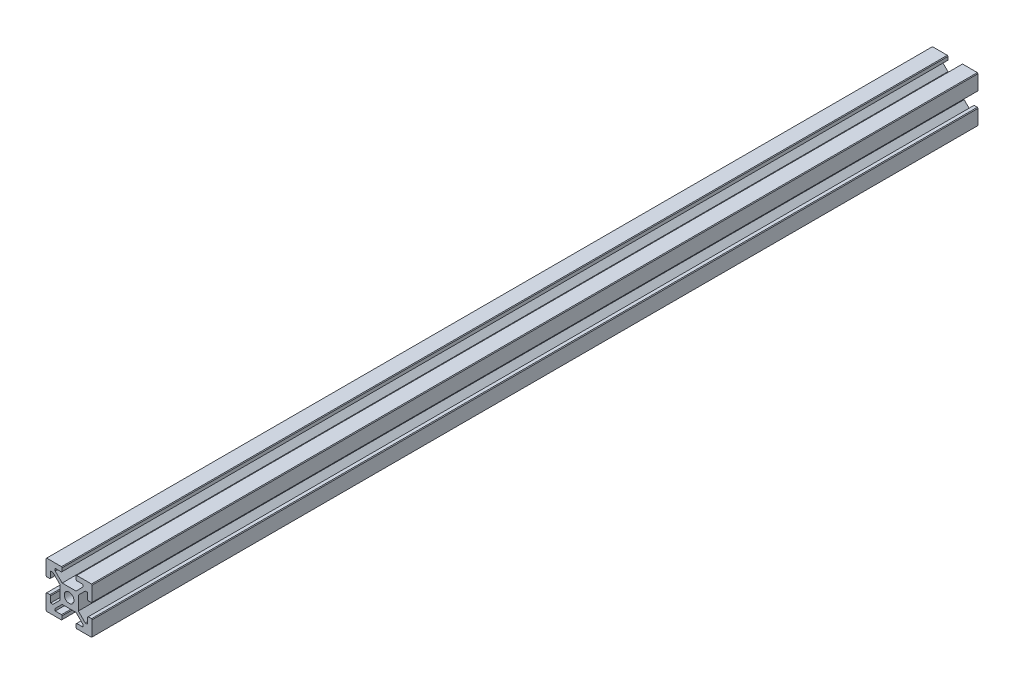
SolidWorks part; units mm, degrees
ref_plane "Front" through (0, 0, 0) normal (0, 0, 1) x (1, 0, 0)
ref_plane "Top" through (0, 0, 0) normal (0, 1, 0) x (1, 0, 0)
ref_plane "Right" through (0, 0, 0) normal (1, 0, 0) x (0, 0, -1)
sketch "Sketch1" plane through (0, 0, 0) normal (0, 0, 1) x (1, 0, 0)
  line L0 (-3, 10) -> (3, 10)
  line L1 (-10, 10) -> (10, 10)
  line L2 (-10, 10) -> (-10, -10)
  line L3 (-10, -10) -> (10, -10)
  line L4 (10, 10) -> (10, -10)
  line L5 (-10, 10) -> (10, -10) construction
  line L6 (-10, -10) -> (10, 10) construction
  line L7 (3, 10) -> (3, 8)
  line L8 (3, 8) -> (6, 8)
  line L9 (-3, 4) -> (3, 4)
  line L10 (0, -11) -> (0, 11) construction
  line L11 (3, 4) -> (6, 7)
  line L12 (6, 7) -> (6, 8)
  line L13 (10, 3) -> (10, -3)
  line L14 (-3, 10) -> (-3, 8)
  line L15 (-3, 8) -> (-6, 8)
  line L16 (-6, 7) -> (-6, 8)
  line L17 (-3, 4) -> (-6, 7)
  line L18 (10, -3) -> (8, -3)
  line L19 (8, -3) -> (8, -6)
  line L20 (7, -6) -> (8, -6)
  line L21 (4, -3) -> (7, -6)
  line L22 (4, 3) -> (4, -3)
  line L23 (4, 3) -> (7, 6)
  line L24 (7, 6) -> (8, 6)
  line L25 (8, 3) -> (8, 6)
  line L26 (10, 3) -> (8, 3)
  line L27 (3, -10) -> (-3, -10)
  line L28 (-3, -10) -> (-3, -8)
  line L29 (-3, -8) -> (-6, -8)
  line L30 (-6, -7) -> (-6, -8)
  line L31 (-3, -4) -> (-6, -7)
  line L32 (3, -4) -> (-3, -4)
  line L33 (3, -4) -> (6, -7)
  line L34 (6, -7) -> (6, -8)
  line L35 (3, -8) -> (6, -8)
  line L36 (3, -10) -> (3, -8)
  line L37 (-10, -3) -> (-10, 3)
  line L38 (-10, 3) -> (-8, 3)
  line L39 (-8, 3) -> (-8, 6)
  line L40 (-7, 6) -> (-8, 6)
  line L41 (-4, 3) -> (-7, 6)
  line L42 (-4, -3) -> (-4, 3)
  line L43 (-4, -3) -> (-7, -6)
  line L44 (-7, -6) -> (-8, -6)
  line L45 (-8, -3) -> (-8, -6)
  line L46 (-10, -3) -> (-8, -3)
  circle A0 centre (0, 0) radius 2.1
  point P0 (0, 0)
  point P18 (0, 10)
  point P22 (0, 4)
  point P53 (0, 0)
  dimension "D1" = 20
  dimension "D2" = 20
  dimension "D3" = 3
  dimension "D4" = 2
  dimension "D5" = 3
  dimension "D6" = 6
  dimension "D7" = 3
  dimension "D8" = 4
extrude "Boss-Extrude1" add sketch "Sketch1" along normal blind 383.54 contours L46 L2 L3 L28 L29 L30 L31 L32 L33 L34 L35 L36 L4 L18 L19 L20 L21 L22 L23 L24 L25 L26 L1 L7 L8 L12 L11 L9 L17 L16 L15 L14 L38 L39 L40 L41 L42 L43 L44 L45 A0 region at (-3.2828, 9, 0)
chamfer "Chamfer1" distance 0.2828 angle 45 20 edges at (-8, 3, 191.77) (-3, 8, 191.77) (-3, 10, 191.77) (-10, 3, 191.77) (-10, 10, 191.77) (-8, -3, 191.77) (-10, -3, 191.77) (-10, -10, 191.77) (-3, -10, 191.77) (-3, -8, 191.77) (3, -8, 191.77) (3, -10, 191.77) (8, -3, 191.77) (10, -10, 191.77) (10, -3, 191.77) (8, 3, 191.77) (10, 3, 191.77) (10, 10, 191.77) (3, 8, 191.77) (3, 10, 191.77)
